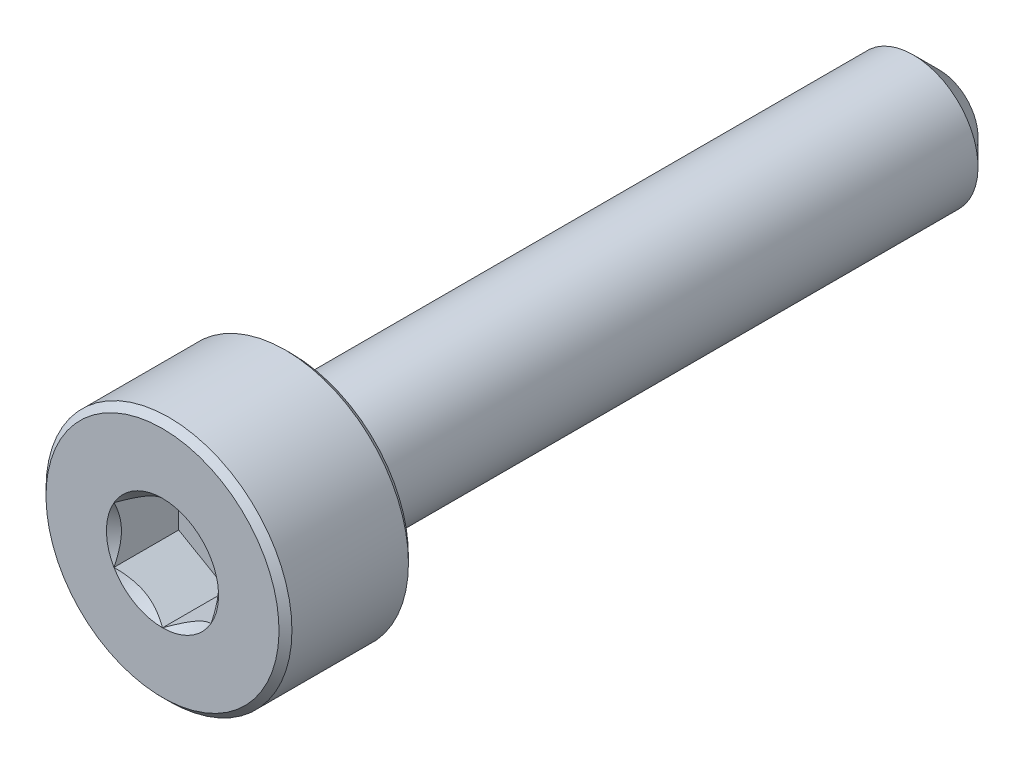
SolidWorks part; units mm, degrees
ref_plane "Front Plane" through (0, 0, 0) normal (0, 0, 1) x (1, 0, 0)
ref_plane "Top Plane" through (0, 0, 0) normal (0, 1, 0) x (1, 0, 0)
ref_plane "Right Plane" through (0, 0, 0) normal (1, 0, 0) x (0, 0, -1)
sketch "Sketch1" plane through (0, 0, 0) normal (1, 0, 0) x (0, 0, -1)
  line L0 (-6, 0) -> (6, 0) construction
  line L1 (6, 0) -> (6, 0.6) construction
  line L2 (6, 0.6) -> (5.6, 1) construction
  line L3 (5.6, 1) -> (5.7, 1) construction
  line L4 (5.7, 1) -> (-4, 1) construction
  line L5 (-4, 1) -> (-4, 1.9) construction
  line L6 (-4, 1.9) -> (-6, 1.9) construction
  line L7 (-6, 1.9) -> (-6, 0) construction
  line L8 (6, 0.6) -> (6, 1) construction
  line L9 (5.975, 1.0433) -> (6.175, 0.6969) construction
  line L10 (6.175, 0.6969) -> (6.375, 1.0433) construction
  line L11 (6.375, 1.0433) -> (5.975, 1.0433) construction
  line L12 (6.175, 1.0433) -> (6.175, 1) construction
  line L13 (6.175, 0.6969) -> (6.175, 0.7402) construction
  line L14 (6.15, 0.7402) -> (6.2, 0.7402) construction
  line L15 (6, 1) -> (6.35, 1) construction
  line L16 (5.9875, 1.0217) -> (6.3625, 1.0217) construction
  line L17 (6, 0) -> (6, -1) construction
  line L18 (-4.1, 1.9) -> (-4, 1.8) construction
  line L19 (-5.9, 1.9) -> (-6, 1.8) construction
  line L20 (-4, 1) -> (-4, 0) construction
  line L21 (-4, 0.5) -> (-0.6667, 0.5) construction
  line L22 (-0.6667, 0.5) -> (2.6667, 0.5) construction
  line L23 (2.6667, 0.5) -> (6, 0.5) construction
  line L24 (-0.6667, 0.5) -> (-0.6667, 1) construction
  line L25 (-0.6667, 1) -> (-0.6667, 1.9) construction
  line L26 (2.6667, 0.5) -> (2.6667, 1.9) construction
  point P0 (-6, 0.75)
  point P3 (5, 1)
  point P4 (0, 0)
  point P18 (2.6667, 1)
  point P22 (6.175, 0.7402)
  point P24 (5.7, 1)
  point P25 (6.175, 1)
  point P28 (6.175, 1.0217)
  point P29 (5, -1)
  point P30 (-0.6667, 1)
  point P31 (-5, 1.9)
  point P37 (-4.35, 1.9)
  point P38 (-5.85, 1.9)
  point P45 (-0.6667, 0.5)
  point P46 (2.6667, 0.5)
  dimension "D1" = 45
  dimension "D2" = 0.05
  dimension "D3" = 0.4
  dimension "D7" = 0.1
  dimension "D8" = 0.1
  dimension "D9" = 0.1
  dimension "D10" = 0.05
  dimension "D11" = 0.25
  dimension "Drive Size" = 1.5
  dimension "Head Diameter" = 3.8
  dimension "Head Height" = 2
  dimension "Thread Pitch" = 0.4
  dimension "Thread Major Diameter" = 2
  dimension "Length" = 10
  dimension "D12" = 0.3
  dimension "D4" = 1
sketch "Sketch2" plane through (0, 0, 0) normal (1, 0, 0) x (0, 0, -1)
  line L0 (-6, 0) -> (-6, 1.8)
  line L1 (-5.9, 1.9) -> (-4.1, 1.9)
  line L2 (-4, 1.8) -> (-4, 1)
  line L3 (-4, 1) -> (5.6, 1)
  line L4 (5.6, 1) -> (6, 0.6)
  line L5 (6, 0.6) -> (6, 0)
  line L6 (-4.1, 1.9) -> (-4, 1.8) construction
  line L7 (6, 0) -> (-6, 0)
  line L8 (-5.9, 1.9) -> (-6, 1.8) construction
  line L9 (-4.1, 1.9) -> (-4, 1.8)
  line L10 (-5.9, 1.9) -> (-6, 1.8)
revolve "Revolve1" add sketch "Sketch2" angle 360 about L7
sketch "Sketch3" plane through (0, 0, 6) normal (0, 0, 1) x (1, 0, 0)
  line L1 (0.75, -0.433) -> (0.75, 0.433)
  line L2 (0.75, 0.433) -> (0, 0.866)
  line L3 (0, 0.866) -> (-0.75, 0.433)
  line L4 (-0.75, 0.433) -> (-0.75, -0.433)
  line L5 (-0.75, -0.433) -> (0, -0.866)
  line L6 (0, -0.866) -> (0.75, -0.433)
  circle A0 centre (0, 0) radius 0.75 construction
extrude "Cut-Extrude1" cut sketch "Sketch3" against normal offset from surface (1 mm away) 1 up to face at (0, 1.8, 4)
sketch "Sketch4" plane through (0, 0, 6) normal (0, 0, 1) x (1, 0, 0)
  circle A0 centre (0, 0) radius 0.866
extrude "Cut-Extrude2" cut sketch "Sketch4" against normal up to vertex (1 mm away) draft 45 up to point (0, 1.9, 5)
ref_plane "Plane1" [suppressed] through (0, 0, -5.7) normal (0, 0, 1) x (1, 0, 0)
split "Split1" [suppressed] bodies to split 106
sketch "Sketch6" [suppressed] plane through (0, 0, -6) normal (0, 0, -1) x (-1, 0, 0)
  circle A0 centre (0, 0) radius 1
curve "Helix/Spiral1" [suppressed] pitch 0.4 height 10.46 turns 26.15
sketch "Sketch7" [suppressed] plane through (0, 0, 0) normal (1, 0, 0) x (0, 0, -1)
  line L0 (5.9875, 1.0217) -> (6.3625, 1.0217)
  line L1 (6.3625, 1.0217) -> (6.2, 0.7402)
  line L2 (6.2, 0.7402) -> (6.15, 0.7402)
  line L3 (6.15, 0.7402) -> (5.9875, 1.0217)
sweep "Cut-Sweep1" [suppressed] cut profiles "Sketch7" path "Helix/Spiral1"
sketch "Sketch8" [suppressed] plane through (0, 0, 4) normal (0, 0, -1) x (-1, 0, 0)
  circle A0 centre (0, 0) radius 1
extrude "Boss-Extrude1" [suppressed] add sketch "Sketch8" along normal through all draft 45
equation "\"D2@Sketch1\" = \"Thread Pitch@Sketch1\" / 8"
equation "\"D3@Sketch1\"= \"Thread Pitch@Sketch1\""
equation "\"D4@Helix/Spiral1\" = \"Thread Pitch@Sketch1\""
equation "\"D7@Sketch1\" = \"Head Height@Sketch1\" * .05"
equation "\"D8@Sketch1\"=\"D7@Sketch1\""
equation "\"D9@Sketch1\"=\"D7@Sketch1\""
equation "\"D10@Sketch1\"=\"D7@Sketch1\"/2"
equation "\"D11@Sketch1\"=\"D10@Sketch1\"*5"
equation "\"D4@Sketch1\"=\"Thread Pitch@Sketch1\"*2.5"
equation "\"D12@Sketch1\"=\"Thread Pitch@Sketch1\"*.75"
